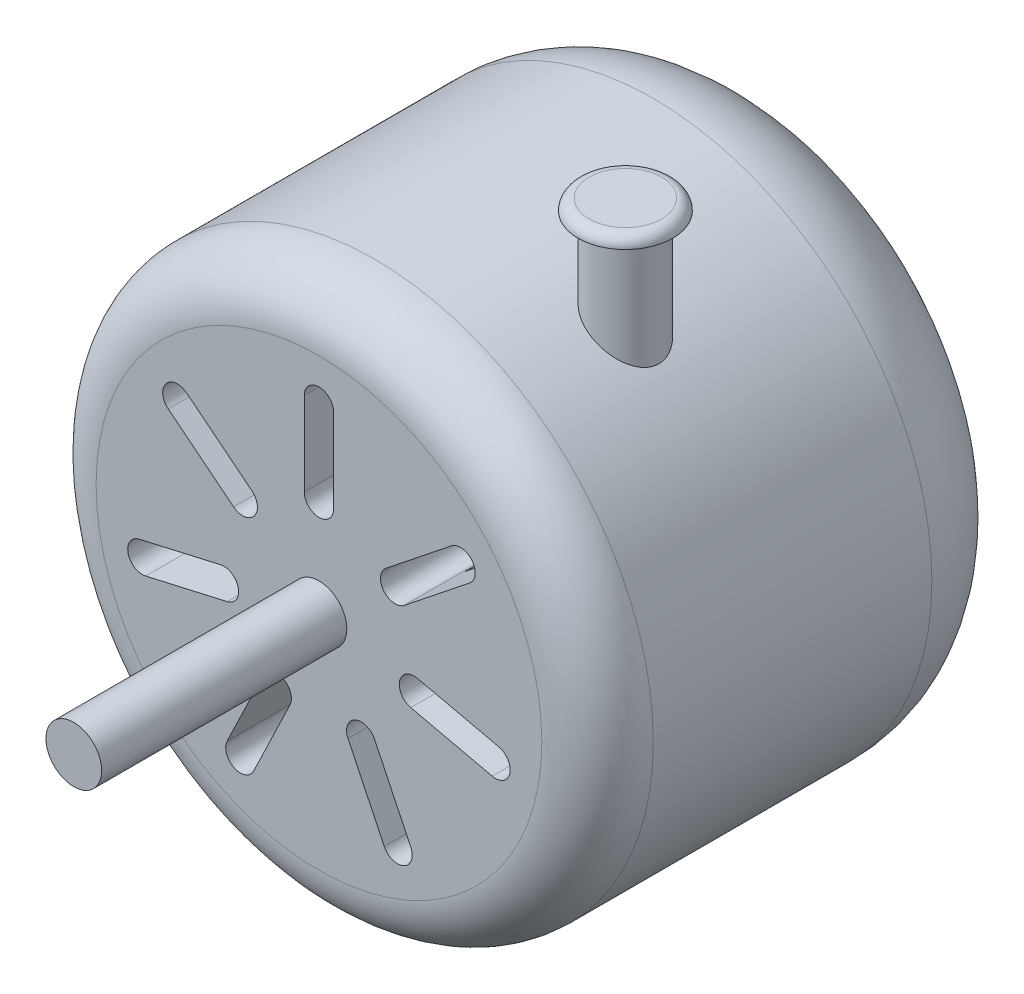
SolidWorks part; units mm, degrees
material "AISI 1010 Steel, hot rolled bar"
ref_plane "Front Plane" through (0, 0, 0) normal (0, 0, 1) x (1, 0, 0)
ref_plane "Top Plane" through (0, 0, 0) normal (0, 1, 0) x (1, 0, 0)
ref_plane "Right Plane" through (0, 0, 0) normal (1, 0, 0) x (0, 0, -1)
sketch "Sketch2" plane through (0, 0, 0) normal (0, 0, 1) x (1, 0, 0)
  circle A0 centre (0, 0) radius 50
  dimension "D1" = 100
extrude "Boss-Extrude1" add sketch "Sketch2" along normal blind 80
fillet "Fillet1" radius 10 1 edges at (50, 0, 80)
fillet "Fillet2" radius 20 1 edges at (50, 0, 0)
sketch "Sketch3" plane through (0, 0, 80) normal (0, 0, 1) x (1, 0, 0)
  line L0 (0, 32.5) -> (0, 17.5) construction
  line L1 (2.6374, 32.5) -> (2.6374, 17.5)
  line L2 (-2.6374, 32.5) -> (-2.6374, 17.5)
  arc A0 (2.6374, 32.5) -> (-2.6374, 32.5) centre (0, 32.5) ccw
  arc A1 (-2.6374, 17.5) -> (2.6374, 17.5) centre (0, 17.5) ccw
  point P2 (0, 25)
  dimension "D1" = 25
  dimension "D2" = 15
extrude "Cut-Extrude1" cut sketch "Sketch3" against normal blind 70
pattern_circular "CirPattern1" count 7 over 360 about axis through (0, 0, 80) along (0, 0, 1) of "Cut-Extrude1"
sketch "Sketch4" plane through (0, 0, 0) normal (0, 0, -1) x (-1, 0, 0)
  arc A0 (0, 20.4743) -> (13.6033, 17.9758) centre (5.5524, 12.4234) cw construction
  arc A1 (14.8593, 18.8419) -> (-0.8662, 21.7303) centre (5.5524, 12.4234) ccw
  arc A2 (12.3473, 17.1096) -> (0.8662, 19.2183) centre (5.5524, 12.4234) ccw
  arc A3 (12.3473, 17.1096) -> (14.8593, 18.8419) centre (13.6033, 17.9758) ccw
  arc A4 (-0.8662, 21.7303) -> (0.8662, 19.2183) centre (0, 20.4743) ccw
  point P3 (7.3191, 22.0424)
extrude "Cut-Extrude2" cut sketch "Sketch4" against normal blind 70
pattern_circular "CirPattern2" count 6 over 360 about axis through (0, 0, 0) along (0, 0, -1) of "Cut-Extrude2"
sketch "Sketch5" plane through (0, 0, 80) normal (0, 0, 1) x (1, 0, 0)
  circle A0 centre (0, 0) radius 5
  dimension "D1" = 10
extrude "Boss-Extrude2" add sketch "Sketch5" along normal mid plane 88
sketch "Sketch6" plane through (0, 0, 0) normal (0, 1, 0) x (1, 0, 0)
  line L0 (50, -70) -> (50, -20) construction
  line L1 (50, -70) -> (-50, -70) construction
  circle A0 centre (25, -50) radius 6
  dimension "D2" = 12
  dimension "D1" = 25
  dimension "D3" = 20
extrude "Boss-Extrude3" add sketch "Sketch6" along normal blind 60
sketch "Sketch7" plane through (0, 60, 0) normal (0, 1, 0) x (1, 0, 0)
  circle A0 centre (25, -50) radius 8.5
  dimension "D1" = 17
extrude "Boss-Extrude4" add sketch "Sketch7" along normal blind 2 separate body
fillet "Fillet3" radius 2 1 edges at (25, 62, 58.5)
